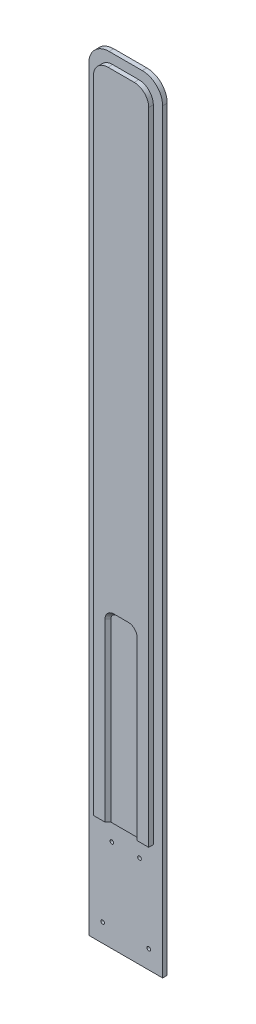
SolidWorks part; units mm, degrees
material "Acrylic (Medium-high impact)"
ref_plane "Front" through (0, 0, 0) normal (0, 0, 1) x (1, 0, 0)
ref_plane "Top" through (0, 0, 0) normal (0, 1, 0) x (1, 0, 0)
ref_plane "Right" through (0, 0, 0) normal (1, 0, 0) x (0, 0, -1)
ref_plane "new front for the battle" through (0, 0, 250.461) normal (0, 0, 1) x (1, 0, 0)
sketch "Sketch1" plane through (0, 0, 250.461) normal (0, 0, 1) x (1, 0, 0)
  line L0 (-76.9, -219) -> (-26.1, -219) construction
  line L1 (-62.9, 238.2) -> (-40.1, 238.2)
  line L2 (-76.9, 224.2) -> (-76.9, -219)
  line L4 (-26.1, 224.2) -> (-26.1, -219)
  line L5 (-76.9, 238.2) -> (-26.1, -219) construction
  line L6 (-76.9, -219) -> (-26.1, 238.2) construction
  line L8 (-76.9, -219) -> (-76.9, -295.2)
  line L9 (-76.9, -295.2) -> (-26.1, -295.2)
  line L10 (-26.1, -219) -> (-26.1, -295.2)
  arc A0 (-40.1, 238.2) -> (-26.1, 224.2) centre (-40.1, 224.2) cw
  arc A1 (-62.9, 238.2) -> (-76.9, 224.2) centre (-62.9, 224.2) ccw
  point P0 (-51.5, 9.6)
  dimension "D5" = 14
  dimension "D1" = 76.2
  dimension "D2" = 457.2
  dimension "D3" = 50.8
  dimension "D4" = 51.5
  dimension "D6" = 219
extrude "Boss-Extrude2" add sketch "Sketch1" along normal mid plane 3.175 separate body
sketch "Sketch2" plane through (0, 0, 250.461) normal (0, 0, 1) x (1, 0, 0)
  line L0 (-40.1, 238.2) -> (-62.9, 238.2) construction
  line L1 (-60.5, 231.6) -> (-42.5, 231.6)
  line L2 (-70.5, 221.6) -> (-70.5, -219)
  line L3 (-70.5, -219) -> (-32.5, -219)
  line L4 (-32.5, 221.6) -> (-32.5, -219)
  line L5 (-76.9, -219) -> (-26.1, -219) construction
  arc A0 (-42.5, 231.6) -> (-32.5, 221.6) centre (-42.5, 221.6) cw
  arc A1 (-60.5, 231.6) -> (-70.5, 221.6) centre (-60.5, 221.6) ccw
  point P4 (-51.5, 231.6)
  point P5 (-51.5, 238.2)
  point P13 (-32.5, 231.6)
  point P16 (-70.5, 231.6)
  dimension "D3" = 10
  dimension "D1" = 6.6
  dimension "D2" = 38
extrude "Boss-Extrude3" add sketch "Sketch2" along normal mid plane 9.525
sketch "Sketch3" plane through (0, 0, 255.2235) normal (0, 0, 1) x (1, 0, 0)
  line L1 (-60.5, -219) -> (-42.5, -219)
  line L2 (-60.5, -219) -> (-60.5, -98)
  line L3 (-56.5, -94) -> (-46.5, -94)
  line L4 (-42.5, -219) -> (-42.5, -98)
  line L5 (-70.5, -219) -> (-32.5, -219) construction
  arc A0 (-46.5, -94) -> (-42.5, -98) centre (-46.5, -98) cw
  arc A1 (-60.5, -98) -> (-56.5, -94) centre (-56.5, -98) cw
  point P6 (-51.5, -219)
  point P10 (-42.5, -94)
  point P13 (-60.5, -94)
  dimension "D3" = 4
  dimension "D1" = 125
  dimension "D2" = 18
extrude "Cut-Extrude1" cut sketch "Sketch3" against normal blind 2
mirror "Mirror2" about plane through (0, 0, 250.461) normal (0, 0, 1) of "Cut-Extrude1"
chamfer "Chamfer1" distance 2 angle 45 10 edges at (-42.5, -158.5, 245.6985) (-60.5, -158.5, 245.6985) (-43.6716, -95.1716, 245.6985) (-59.3284, -95.1716, 245.6985) (-51.5, -94, 245.6985) (-42.5, -158.5, 255.2235) (-60.5, -158.5, 255.2235) (-43.6716, -95.1716, 255.2235) (-59.3284, -95.1716, 255.2235) (-51.5, -94, 255.2235)
sketch "Sketch4" plane through (0, 0, 252.0485) normal (0, 0, 1) x (1, 0, 0)
  line L0 (-76.9, -231.7) -> (-26.1, -231.7) construction
  line L1 (-76.9, 224.2) -> (-76.9, -295.2) construction
  line L2 (-26.1, -295.2) -> (-26.1, 224.2) construction
  line L3 (-61.025, -231.7) -> (-67.375, -282.5) construction
  line L4 (-67.375, -282.5) -> (-35.625, -282.5) construction
  line L5 (-35.625, -282.5) -> (-41.975, -231.7) construction
  line L7 (-40.5, -219) -> (-32.5, -219) construction
  line L8 (-76.9, -295.2) -> (-26.1, -295.2) construction
  circle A0 centre (-61.025, -231.7) radius 1.25
  circle A1 centre (-41.975, -231.7) radius 1.25
  circle A2 centre (-35.625, -282.5) radius 1.25
  circle A3 centre (-67.375, -282.5) radius 1.25
  point P10 (-51.5, -282.5)
  point P14 (-51.5, -231.7)
  dimension "D1" = 2.5
  dimension "D2" = 19.05
  dimension "D3" = 31.75
  dimension "D4" = 12.7
  dimension "D5" = 12.7
  dimension "D6" = 50.8
extrude "Cut-Extrude2" cut sketch "Sketch4" against normal through all
